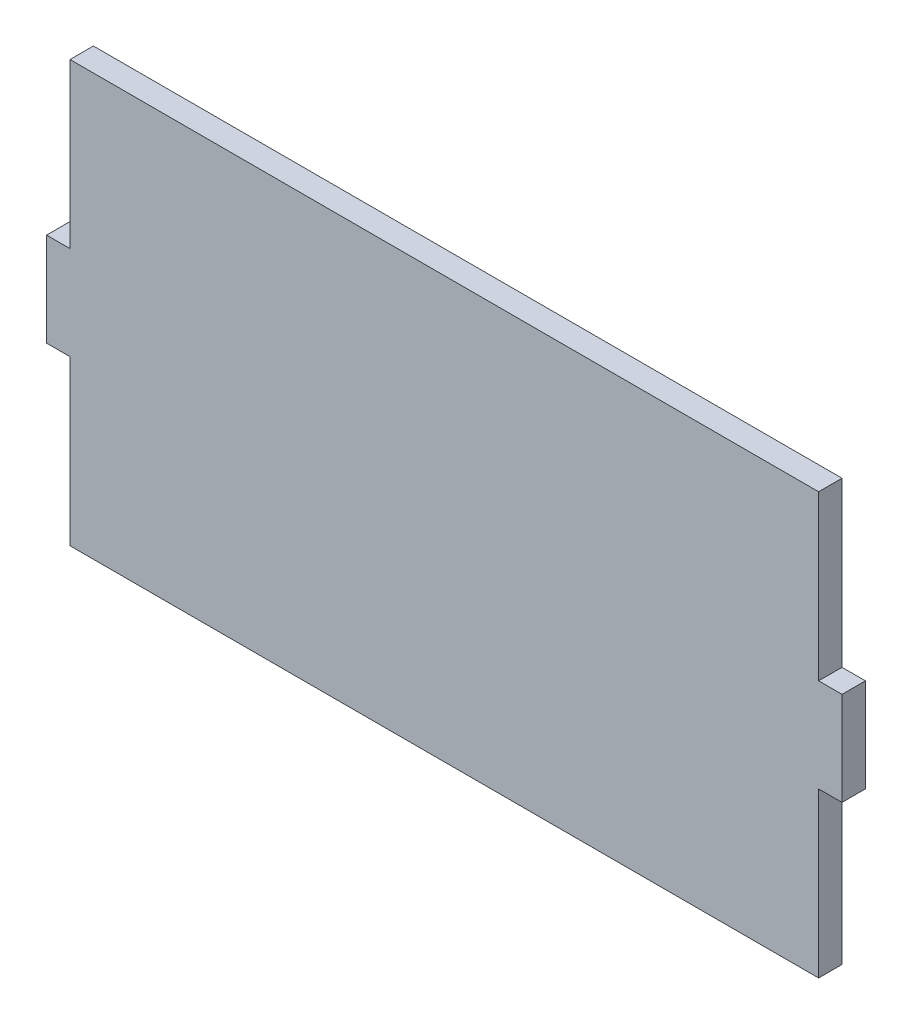
SolidWorks part; units mm, degrees
ref_plane "Front Plane" through (0, 0, 0) normal (0, 0, 1) x (1, 0, 0)
ref_plane "Top Plane" through (0, 0, 0) normal (0, 1, 0) x (1, 0, 0)
ref_plane "Right Plane" through (0, 0, 0) normal (1, 0, 0) x (0, 0, -1)
sketch "Sketch1" plane through (0, 0, 0) normal (0, 0, 1) x (1, 0, 0)
  line L1 (0, 0) -> (101.6, 0)
  line L2 (0, 0) -> (0, 57.15)
  line L3 (0, 57.15) -> (101.6, 57.15)
  line L4 (101.6, 0) -> (101.6, 57.15)
  dimension "D1" = 57.15
  dimension "D2" = 101.6
extrude "Boss-Extrude1" add sketch "Sketch1" along normal blind 3.175
sketch "Sketch2" plane through (0, 0, 3.175) normal (0, 0, 1) x (1, 0, 0)
  line L0 (0, 57.15) -> (0, 0) construction
  line L1 (0, 34.925) -> (-3.175, 34.925)
  line L2 (0, 34.925) -> (0, 22.225)
  line L3 (0, 22.225) -> (-3.175, 22.225)
  line L4 (-3.175, 34.925) -> (-3.175, 22.225)
  line L5 (50.8, 57.15) -> (50.8, 0) construction
  line L6 (101.6, 57.15) -> (0, 57.15) construction
  line L7 (0, 0) -> (101.6, 0) construction
  line L8 (101.6, 34.925) -> (101.6, 22.225)
  line L9 (101.6, 22.225) -> (104.775, 22.225)
  line L10 (101.6, 34.925) -> (104.775, 34.925)
  line L11 (104.775, 34.925) -> (104.775, 22.225)
  point P6 (0, 28.575)
  point P7 (-3.175, 28.575)
  dimension "D1" = 3.175
  dimension "D2" = 12.7
extrude "Boss-Extrude2" add sketch "Sketch2" against normal blind 3.175
